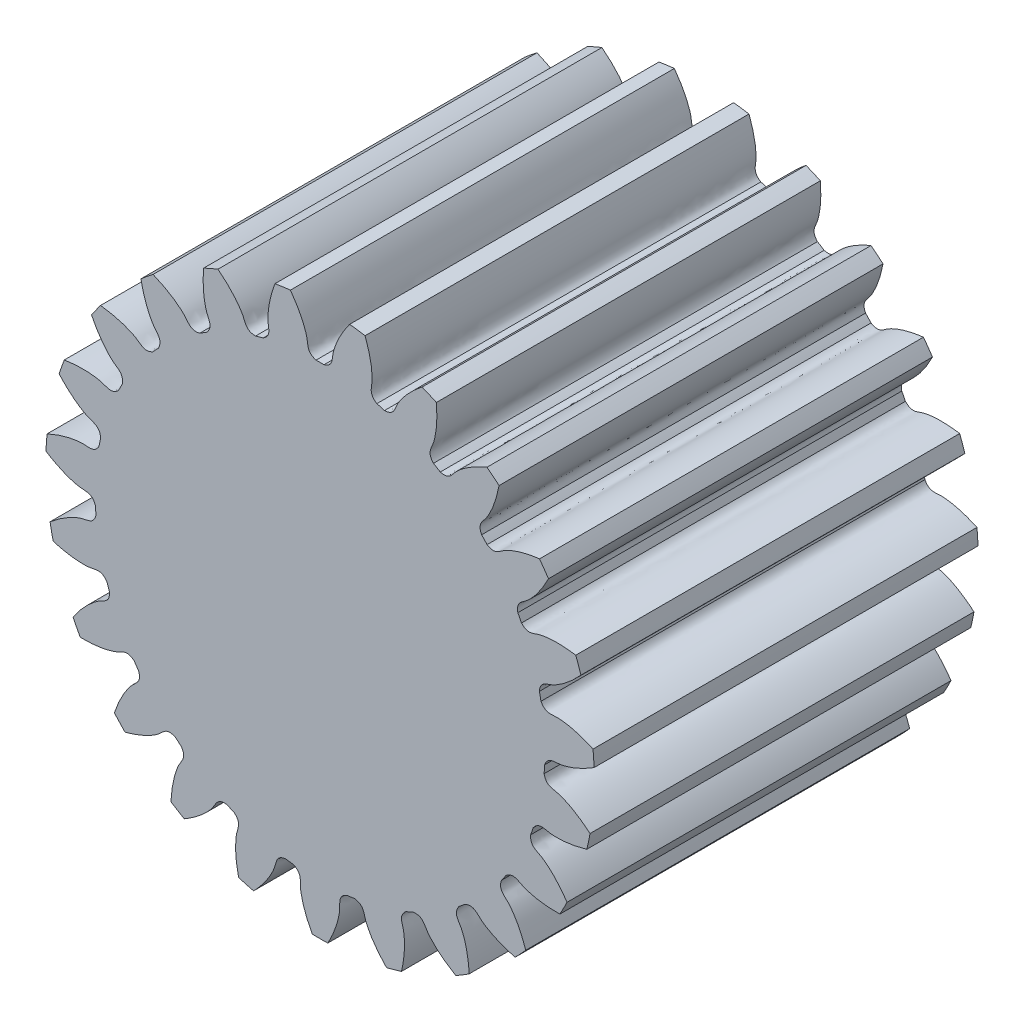
SolidWorks part; units mm, degrees
ref_plane "前视基准面" through (0, 0, 0) normal (0, 0, 1) x (1, 0, 0)
ref_plane "上视基准面" through (0, 0, 0) normal (0, 1, 0) x (1, 0, 0)
ref_plane "右视基准面" through (0, 0, 0) normal (1, 0, 0) x (0, 0, -1)
sketch "草图1" plane through (0, 0, 0) normal (0, 0, 1) x (1, 0, 0)
  circle A0 centre (0, 0) radius 12.5
extrude "凸台-拉伸1" add sketch "草图1" along normal blind 30
ref_axis "基准轴1" through (0, 0, -1.5) along (0, 0, 1)
sketch "草图2" plane through (0, 0, 0) normal (0, 0, 1) x (1, 0, 0)
  line L0 (0, 0) -> (0, 12.5) construction
  circle A0 centre (0, 0) radius 12.5 construction
  arc A1 (0.1814, 10.2484) -> (-0.1814, 10.2484) centre (0, 0) ccw
  arc A2 (3.1817, 14.1862) -> (-3.1817, 14.1862) centre (0, 0) ccw
  spline S0 degree 3 poles (0.1814, 10.2484) (0.5777, 10.3668) (0.5438, 10.6338) (0.5929, 10.8972) (0.5995, 10.9289) (0.6077, 10.9648) (0.6176, 11.0046) (0.6294, 11.0484) (0.6433, 11.0961) (0.6595, 11.1477) (0.6781, 11.203) (0.6992, 11.262) (0.723, 11.3247) (0.7498, 11.3908) (0.7795, 11.4604) (0.8124, 11.5333) (0.8485, 11.6094) (0.8882, 11.6887) (0.9314, 11.7709) (0.9783, 11.8561) (1.0291, 11.9441) (1.0839, 12.0347) (1.1428, 12.1279) (1.2059, 12.2235) (1.2734, 12.3214) (1.3454, 12.4214) (1.4219, 12.5234) (1.5031, 12.6273) (1.5891, 12.7328) (1.68, 12.84) (1.7759, 12.9485) (1.8768, 13.0583) (1.9829, 13.1691) (2.0943, 13.2809) (2.211, 13.3934) (2.3331, 13.5065) (2.4606, 13.62) (2.5937, 13.7338) (2.7324, 13.8476) (2.9271, 14.001) (3.0783, 14.1128) (3.1817, 14.1862) knots 0 0 0 0 0.147387 0.15296 0.159389 0.166677 0.174821 0.183823 0.193683 0.204399 0.215973 0.228404 0.241693 0.255839 0.270842 0.286703 0.303421 0.320996 0.339428 0.358718 0.378866 0.39987 0.421732 0.444451 0.468028 0.492462 0.517753 0.543901 0.570907 0.59877 0.627491 0.657069 0.687504 0.718796 0.750946 0.783953 0.817818 0.85254 0.888119 0.924555 1 1 1 1
  spline S1 degree 3 poles (-0.1814, 10.2484) (-0.5777, 10.3668) (-0.5438, 10.6338) (-0.5929, 10.8972) (-0.5995, 10.9289) (-0.6077, 10.9648) (-0.6176, 11.0046) (-0.6294, 11.0484) (-0.6433, 11.0961) (-0.6595, 11.1477) (-0.6781, 11.203) (-0.6992, 11.262) (-0.723, 11.3247) (-0.7498, 11.3908) (-0.7795, 11.4604) (-0.8124, 11.5333) (-0.8485, 11.6094) (-0.8882, 11.6887) (-0.9314, 11.7709) (-0.9783, 11.8561) (-1.0291, 11.9441) (-1.0839, 12.0347) (-1.1428, 12.1279) (-1.2059, 12.2235) (-1.2734, 12.3214) (-1.3454, 12.4214) (-1.4219, 12.5234) (-1.5031, 12.6273) (-1.5891, 12.7328) (-1.68, 12.84) (-1.7759, 12.9485) (-1.8768, 13.0583) (-1.9829, 13.1691) (-2.0943, 13.2809) (-2.211, 13.3934) (-2.3331, 13.5065) (-2.4606, 13.62) (-2.5937, 13.7338) (-2.7324, 13.8476) (-2.9271, 14.001) (-3.0783, 14.1128) (-3.1817, 14.1862) knots 0 0 0 0 0.147387 0.15296 0.159389 0.166677 0.174821 0.183823 0.193683 0.204399 0.215973 0.228404 0.241693 0.255839 0.270842 0.286703 0.303421 0.320996 0.339428 0.358718 0.378866 0.39987 0.421732 0.444451 0.468028 0.492462 0.517753 0.543901 0.570907 0.59877 0.627491 0.657069 0.687504 0.718796 0.750946 0.783953 0.817818 0.85254 0.888119 0.924555 1 1 1 1
extrude "切除-拉伸1" cut sketch "草图2" along normal through all
pattern_circular "阵列(圆周)1" count 23 every 15.652 about axis through (0, 0, -1.5) along (0, 0, 1) of "切除-拉伸1"
sketch "草图3" plane through (0, 0, 0) normal (0, 0, 1) x (1, 0, 0)
  circle A0 centre (0, 0) radius 11.5 construction
  dimension "Dn" = 23
sketch "草图4" plane through (0, 0, 30) normal (0, 0, 1) x (1, 0, 0)
  circle A0 centre (0, 0) radius 23.8848
extrude "切除-拉伸2" cut sketch "草图4" against normal offset from surface (12.5 mm away) 17.5 up to face at (0, 0, 0)
